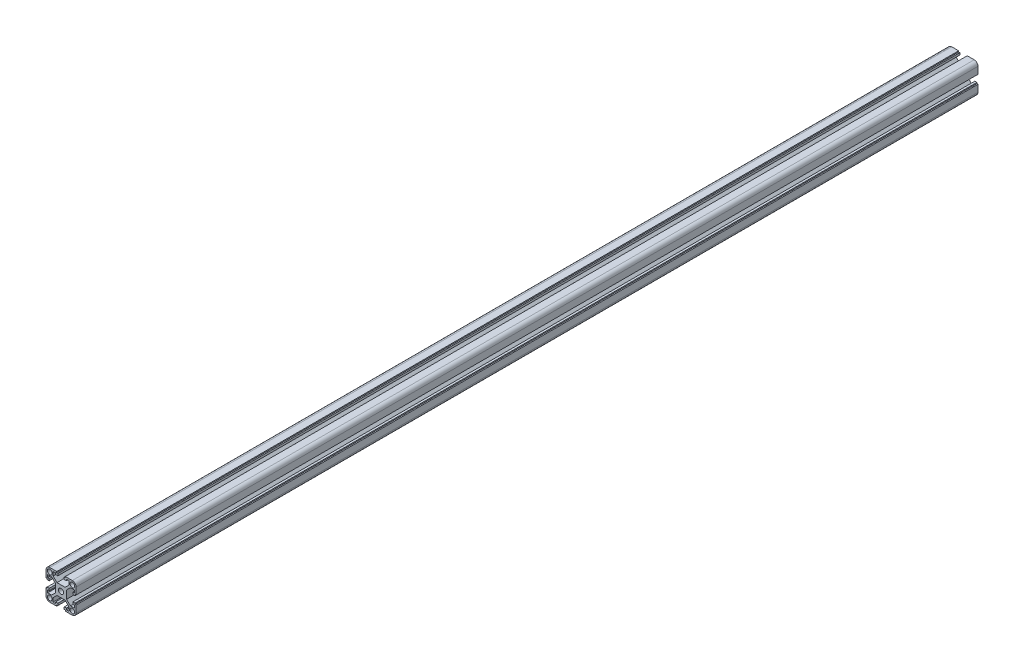
SolidWorks part; units mm, degrees
material "АД1 ГОСТ 4784-97"
ref_plane "Спереди" through (0, 0, 0) normal (0, 0, 1) x (1, 0, 0)
ref_plane "Сверху" through (0, 0, 0) normal (0, 1, 0) x (1, 0, 0)
ref_plane "Справа" through (0, 0, 0) normal (1, 0, 0) x (0, 0, -1)
ref_axis "ОсьX" through (-88.99, 0, 0) along (1, 0, 0)
ref_axis "ОсьZ" through (0, 55, 0) along (0, -1, 0)
ref_axis "ОсьY" through (0, 0, -88.99) along (0, 0, 1)
sketch "Эскиз1" plane through (0, 0, 0) normal (0, 0, 1) x (1, 0, 0)
  line L0 (-15, 20) -> (-5.7274, 20)
  line L1 (-5.7274, 20) -> (-5.7274, 18.5304)
  line L2 (-5.7274, 18.5304) -> (-4.25, 18.5304)
  line L3 (-4.25, 18.5304) -> (-4.25, 15.732)
  line L4 (-4.25, 15.732) -> (-7.1118, 15.732)
  line L5 (-7.1118, 15.732) -> (-7.1118, 17.7)
  line L6 (-7.1118, 17.7) -> (-10.5, 17.7)
  line L7 (-10.5, 17.7) -> (-10.5, 12.4799)
  line L8 (-10.5, 12.4799) -> (-5.4201, 7.4)
  line L9 (-20, 15) -> (-20, 5.7274)
  line L10 (0, 0) -> (0, 8.4096) construction
  line L11 (-15, 15) -> (0, 0) construction
  line L12 (10.5, 12.4799) -> (5.4201, 7.4)
  line L13 (10.5, 17.7) -> (10.5, 12.4799)
  line L14 (7.1118, 17.7) -> (10.5, 17.7)
  line L15 (7.1118, 15.732) -> (7.1118, 17.7)
  line L16 (4.25, 15.732) -> (7.1118, 15.732)
  line L17 (4.25, 18.5304) -> (4.25, 15.732)
  line L18 (5.7274, 18.5304) -> (4.25, 18.5304)
  line L19 (5.7274, 20) -> (5.7274, 18.5304)
  line L20 (15, 20) -> (5.7274, 20)
  line L21 (-5.4201, 7.4) -> (5.4201, 7.4)
  line L22 (-8.8445, 0) -> (0, 0) construction
  line L23 (-12.4799, 10.5) -> (-7.4, 5.4201)
  line L24 (-17.7, 10.5) -> (-12.4799, 10.5)
  line L25 (-17.7, 7.1118) -> (-17.7, 10.5)
  line L26 (-15.732, 7.1118) -> (-17.7, 7.1118)
  line L27 (-15.732, 4.25) -> (-15.732, 7.1118)
  line L28 (-18.5304, 4.25) -> (-15.732, 4.25)
  line L29 (-18.5304, 5.7274) -> (-18.5304, 4.25)
  line L30 (-20, 5.7274) -> (-18.5304, 5.7274)
  line L31 (18.5304, 5.7274) -> (18.5304, 4.25)
  line L32 (18.5304, 4.25) -> (15.732, 4.25)
  line L33 (15.732, 4.25) -> (15.732, 7.1118)
  line L34 (15.732, 7.1118) -> (17.7, 7.1118)
  line L35 (12.4799, 10.5) -> (7.4, 5.4201)
  line L36 (17.7, 10.5) -> (12.4799, 10.5)
  line L37 (17.7, 7.1118) -> (17.7, 10.5)
  line L38 (20, 5.7274) -> (18.5304, 5.7274)
  line L39 (20, 15) -> (20, 5.7274)
  line L40 (20, -15) -> (20, -5.7274)
  line L41 (20, -5.7274) -> (18.5304, -5.7274)
  line L42 (17.7, -7.1118) -> (17.7, -10.5)
  line L43 (17.7, -10.5) -> (12.4799, -10.5)
  line L44 (12.4799, -10.5) -> (7.4, -5.4201)
  line L45 (15.732, -7.1118) -> (17.7, -7.1118)
  line L46 (15.732, -4.25) -> (15.732, -7.1118)
  line L47 (18.5304, -4.25) -> (15.732, -4.25)
  line L48 (18.5304, -5.7274) -> (18.5304, -4.25)
  line L49 (-20, -5.7274) -> (-18.5304, -5.7274)
  line L50 (-18.5304, -5.7274) -> (-18.5304, -4.25)
  line L51 (-18.5304, -4.25) -> (-15.732, -4.25)
  line L52 (-15.732, -4.25) -> (-15.732, -7.1118)
  line L53 (-15.732, -7.1118) -> (-17.7, -7.1118)
  line L54 (-17.7, -7.1118) -> (-17.7, -10.5)
  line L55 (-17.7, -10.5) -> (-12.4799, -10.5)
  line L56 (-12.4799, -10.5) -> (-7.4, -5.4201)
  line L57 (-5.4201, -7.4) -> (5.4201, -7.4)
  line L58 (15, -20) -> (5.7274, -20)
  line L59 (5.7274, -20) -> (5.7274, -18.5304)
  line L60 (5.7274, -18.5304) -> (4.25, -18.5304)
  line L61 (4.25, -18.5304) -> (4.25, -15.732)
  line L62 (4.25, -15.732) -> (7.1118, -15.732)
  line L63 (7.1118, -15.732) -> (7.1118, -17.7)
  line L64 (7.1118, -17.7) -> (10.5, -17.7)
  line L65 (10.5, -17.7) -> (10.5, -12.4799)
  line L66 (10.5, -12.4799) -> (5.4201, -7.4)
  line L67 (-20, -15) -> (-20, -5.7274)
  line L68 (-10.5, -12.4799) -> (-5.4201, -7.4)
  line L69 (-10.5, -17.7) -> (-10.5, -12.4799)
  line L70 (-7.1118, -17.7) -> (-10.5, -17.7)
  line L71 (-7.1118, -15.732) -> (-7.1118, -17.7)
  line L72 (-4.25, -15.732) -> (-7.1118, -15.732)
  line L73 (-4.25, -18.5304) -> (-4.25, -15.732)
  line L74 (-5.7274, -18.5304) -> (-4.25, -18.5304)
  line L75 (-5.7274, -20) -> (-5.7274, -18.5304)
  line L76 (-15, -20) -> (-5.7274, -20)
  line L77 (-7.4, 5.4201) -> (-7.4, -5.4201)
  line L78 (7.4, 5.4201) -> (7.4, -5.4201)
  circle A0 centre (0, 0) radius 3.4
  circle A1 centre (-15, 15) radius 3.15
  arc A2 (-15, 20) -> (-20, 15) centre (-15, 15) ccw
  arc A3 (15, 20) -> (20, 15) centre (15, 15) cw
  circle A4 centre (15, 15) radius 3.15
  circle A5 centre (15, -15) radius 3.15
  arc A6 (15, -20) -> (20, -15) centre (15, -15) ccw
  arc A7 (-15, -20) -> (-20, -15) centre (-15, -15) cw
  circle A8 centre (-15, -15) radius 3.15
  dimension "D1" = 6.8
  dimension "D2" = 6.3
  dimension "D3" = 40
  dimension "D8" = 30
  dimension "D4" = 2.3
  dimension "D5" = 1.35
  dimension "D6" = 21
  dimension "D7" = 8.5
  dimension "D9" = 45
  dimension "D10" = 2.8
  dimension "D11" = 4
  dimension "D13" = 40
extrude "Бобышка-Вытянуть1" add sketch "Эскиз1" along normal mid plane 1200
